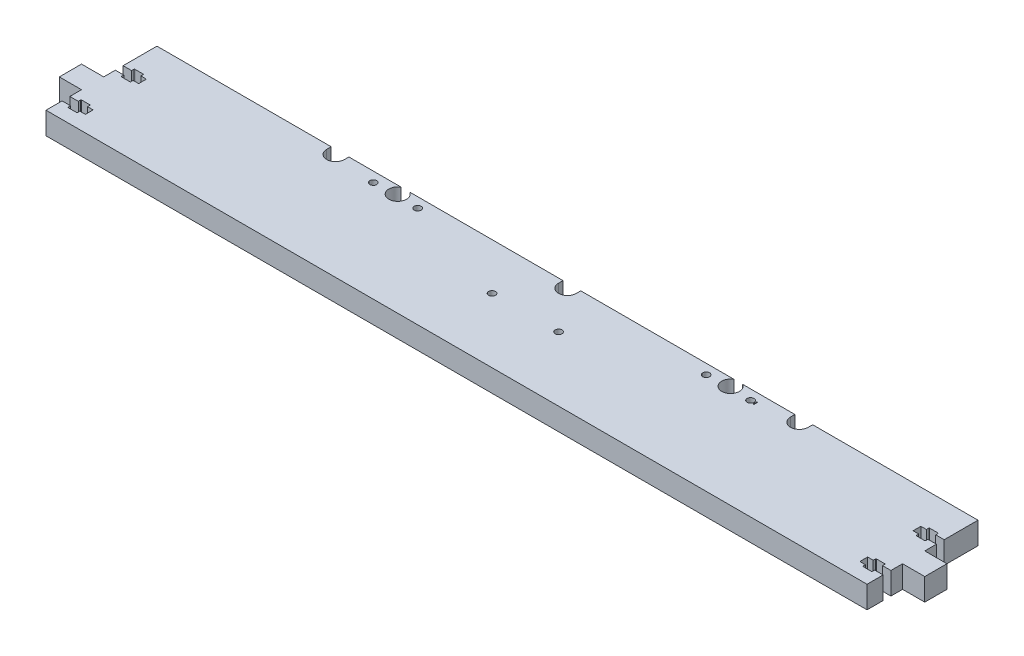
SolidWorks part; units mm, degrees
ref_plane "Front Plane" through (0, 0, 0) normal (0, 0, 1) x (1, 0, 0)
ref_plane "Top Plane" through (0, 0, 0) normal (0, 1, 0) x (1, 0, 0)
ref_plane "Right Plane" through (0, 0, 0) normal (1, 0, 0) x (0, 0, -1)
sketch "Sketch1" plane through (0, 0, 0) normal (0, 1, 0) x (1, 0, 0)
  line L0 (0, 25) -> (0, -25)
  line L1 (-185, 25) -> (0, 25)
  line L2 (-185, 25) -> (-185, -25) construction
  line L3 (-185, -25) -> (0, -25)
  line L4 (-185, -4) -> (-195, -4) construction
  line L5 (-185, 25) -> (0, 0) construction
  line L6 (-185, -25) -> (0, 0) construction
  line L7 (-185, -9) -> (-195, -9)
  line L8 (-195, -9) -> (-195, 1)
  line L9 (-195, 1) -> (-185, 1)
  line L10 (-185, 1) -> (-185, 25)
  line L11 (-185, -9) -> (-185, -25)
  line L47 (0, -25) -> (0, 25) construction
  line L89 (0, -25) -> (0, 25) construction
  point P0 (0, 0)
  dimension "D1" = 185
  dimension "D25" = 25
  dimension "D4" = 50
  dimension "D3" = 21
  dimension "D5" = 10
  dimension "D6" = 10
  dimension "D7" = 5
extrude "MainBody" add sketch "Sketch1" along normal blind 10 contours L3 region at (-93.5428, 0, 0.0428)
sketch "Sketch5" plane through (0, 10, 0) normal (0, 1, 0) x (1, 0, 0)
  line L0 (-185, 8) -> (-174.5, 8) construction
  line L1 (-185, 1) -> (-185, 25) construction
  line L2 (-185, 9.75) -> (-174.5, 9.75) construction
  line L3 (-174.5, 9.75) -> (-174.5, 6.25) construction
  line L4 (-174.5, 6.25) -> (-185, 6.25) construction
  line L5 (-185, 9.75) -> (-181.2, 9.75)
  line L6 (-181.2, 9.75) -> (-181.2, 10.75)
  line L7 (-180.95, 11) -> (-177.25, 11)
  line L8 (-177, 10.75) -> (-177, 9.75)
  line L9 (-177, 9.75) -> (-174.5, 9.75)
  line L10 (-174.5, 9.75) -> (-174.5, 6.25)
  line L11 (-185, 6.25) -> (-185, 9.75)
  line L12 (-195, -9) -> (-195, 1) construction
  line L13 (-185, 6.25) -> (-174.5, 6.25) construction
  line L14 (-177, 6.25) -> (-174.5, 6.25)
  line L15 (-177, 5.25) -> (-177, 6.25)
  line L16 (-180.95, 5) -> (-177.25, 5)
  line L17 (-181.2, 6.25) -> (-181.2, 5.25)
  line L18 (-185, 6.25) -> (-181.2, 6.25)
  line L19 (-185, 1) -> (-185, -9) construction
  line L20 (-195, -4) -> (-185, -4) construction
  line L21 (-195, -9) -> (-195, 1) construction
  line L22 (-185, -14.25) -> (-174.5, -14.25) construction
  line L23 (-174.5, -14.25) -> (-185, -14.25) construction
  line L24 (-174.5, -17.75) -> (-174.5, -14.25) construction
  line L25 (-185, -17.75) -> (-174.5, -17.75) construction
  line L26 (-185, -16) -> (-174.5, -16) construction
  line L27 (-185, -14.25) -> (-181.2, -14.25)
  line L28 (-181.2, -14.25) -> (-181.2, -13.25)
  line L29 (-180.95, -13) -> (-177.25, -13)
  line L30 (-177, -13.25) -> (-177, -14.25)
  line L31 (-177, -14.25) -> (-174.5, -14.25)
  line L32 (-185, -14.25) -> (-185, -17.75)
  line L33 (-174.5, -17.75) -> (-174.5, -14.25)
  line L34 (-177, -17.75) -> (-174.5, -17.75)
  line L35 (-177, -18.75) -> (-177, -17.75)
  line L36 (-180.95, -19) -> (-177.25, -19)
  line L37 (-181.2, -17.75) -> (-181.2, -18.75)
  line L38 (-185, -17.75) -> (-181.2, -17.75)
  line L39 (-185, 6.25) -> (-174.5, 6.25) construction
  arc A0 (-177.25, 11) -> (-177, 10.75) centre (-177.25, 10.75) cw
  arc A1 (-181.2, 10.75) -> (-180.95, 11) centre (-180.95, 10.75) cw
  arc A2 (-181.2, 5.25) -> (-180.95, 5) centre (-180.95, 5.25) ccw
  arc A3 (-177.25, 5) -> (-177, 5.25) centre (-177.25, 5.25) ccw
  arc A4 (-177.25, -13) -> (-177, -13.25) centre (-177.25, -13.25) cw
  arc A5 (-181.2, -13.25) -> (-180.95, -13) centre (-180.95, -13.25) cw
  arc A6 (-181.2, -18.75) -> (-180.95, -19) centre (-180.95, -18.75) ccw
  arc A7 (-177.25, -19) -> (-177, -18.75) centre (-177.25, -18.75) ccw
  point P6 (-195, -4)
  point P17 (-177, 11)
  point P20 (-181.2, 11)
  point P29 (-181.2, 5)
  point P30 (-177, 5)
  point P61 (-177, -13)
  point P62 (-181.2, -13)
  point P63 (-181.2, -19)
  point P64 (-177, -19)
  dimension "D8" = 0.25
  dimension "D1" = 10.5
  dimension "D2" = 1.75
  dimension "D4" = 4.2
  dimension "D5" = 8
  dimension "D6" = 3
  dimension "D7" = 12
extrude "ScrewCutouts" cut sketch "Sketch5" against normal through all
mirror "Mirror1" about plane through (0, 0, 0) normal (1, 0, 0) of "ScrewCutouts", "MainBody"
sketch "Sketch3" plane through (0, 10, 0) normal (0, 1, 0) x (1, 0, 0)
  line L0 (2, 25) -> (2, -25) construction
  line L1 (-185, 25) -> (185, 25) construction
  line L2 (-185, -25) -> (185, -25) construction
  line L3 (-63, 20.5) -> (-83, 20.5) construction
  line L4 (-73, 17.5) -> (-73, 25.5) construction
  line L5 (77, 17.5) -> (77, 25.5) construction
  line L6 (67, 20.5) -> (87, 20.5) construction
  circle A0 centre (-73, 21.5) radius 4
  circle A1 centre (-83, 20.5) radius 1.55
  circle A2 centre (-63, 20.5) radius 1.55
  circle A3 centre (67, 20.5) radius 1.55
  circle A4 centre (87, 20.5) radius 1.55
  circle A5 centre (77, 21.5) radius 4
  dimension "D2" = 8
  dimension "D4" = 3.1
  dimension "D1" = 3.5
  dimension "D5" = 75
  dimension "D6" = 2
  dimension "D3" = 10
  dimension "D7" = 1
extrude "RodCutouts" cut sketch "Sketch3" against normal through all
sketch "Sketch6" plane through (0, 10, 0) normal (0, 1, 0) x (1, 0, 0)
  line L0 (-73, 21.5) -> (77, 21.5) construction
  line L1 (2, 21.5) -> (2, -25) construction
  line L2 (-185, -25) -> (185, -25) construction
  line L3 (17, 4) -> (-13, 4) construction
  line L4 (-71.0635, 25) -> (75.0635, 25) construction
  circle A0 centre (-13, 4) radius 1.55
  circle A1 centre (17, 4) radius 1.55
  point P13 (2, 4)
  dimension "D3" = 21
  dimension "D1" = 3.1
  dimension "D2" = 15
extrude "Cut-Extrude1" cut sketch "Sketch6" against normal through all
sketch "Sketch7" plane through (0, 10, 0) normal (0, 1, 0) x (1, 0, 0)
  line L0 (-73, 21.5) -> (77, 21.5) construction
  line L1 (2, 21.5) -> (2, -25) construction
  line L3 (-102.5, 25) -> (-102.5, 23) construction
  line L4 (-185, 25) -> (-74.9365, 25) construction
  line L5 (-98.5, 25) -> (-98.5, 23)
  line L6 (-106.5, 25) -> (-106.5, 23)
  line L7 (106.5, 25) -> (106.5, 23) construction
  line L8 (102.5, 25) -> (102.5, 23)
  line L9 (110.5, 25) -> (110.5, 23)
  line L12 (-185, -25) -> (185, -25) construction
  arc A0 (-98.5, 25) -> (-106.5, 25) centre (-102.5, 25) ccw
  arc A1 (-106.5, 23) -> (-98.5, 23) centre (-102.5, 23) ccw
  arc A2 (102.5, 25) -> (110.5, 25) centre (106.5, 25) cw
  arc A3 (110.5, 23) -> (102.5, 23) centre (106.5, 23) cw
  point P12 (-102.5, 24)
  point P19 (106.5, 24)
  dimension "D1" = 4
  dimension "D2" = 2
  dimension "D3" = 104.5
extrude "BedAdjustmentScrewCutout" cut sketch "Sketch7" against normal through all
sketch "Sketch8" plane through (0, 10, 0) normal (0, 1, 0) x (1, 0, 0)
  line L0 (88.35, 20.5) -> (89.35, 20.5) construction
  line L1 (88.55, 20.5) -> (88.55, 25) construction
  line L2 (88.35, 20.5) -> (89.35, 21.5)
  line L3 (89.35, 21.5) -> (89.35, 19.5)
  line L4 (88.35, 20.5) -> (89.35, 19.5)
  line L5 (78.9365, 25) -> (102.5, 25) construction
  circle A1 centre (87, 20.5) radius 1.55 construction
  point P9 (89.35, 20.5)
  dimension "D1" = 1
  dimension "D2" = 1
  dimension "D3" = 0.2
extrude "DirectionKey" cut sketch "Sketch8" against normal through all
sketch "Sketch9" plane through (0, 10, 0) normal (0, 1, 0) x (1, 0, 0)
  line L0 (-13, 4) -> (17, 4) construction
  line L1 (2, 4) -> (2, 25) construction
  line L2 (-71.0635, 25) -> (75.0635, 25) construction
  line L3 (2, 27) -> (2, 23) construction
  line L4 (6, 27) -> (6, 23)
  line L5 (-2, 27) -> (-2, 23)
  arc A0 (6, 27) -> (-2, 27) centre (2, 27) ccw
  arc A1 (-2, 23) -> (6, 23) centre (2, 23) ccw
  point P10 (2, 25)
  dimension "D1" = 4
  dimension "D2" = 2
extrude "Cut-Extrude2" cut sketch "Sketch9" against normal through all
equation "\"Y-ROD-SPACING\"=75"
equation "\"Y-BED-OFFSET\"=2"
equation "\"T-SLOT-NUT-FILLET-RADIUS\"=0.25"
equation "\"T-SLOT-SCREW-SHAFT-RADIUS\"=1.75"
equation "\"T-SLOT-SCREW-SHAFT-CUTOUT-LENGTH\"=10.5"
equation "\"T-SLOT-NUT-DEPTH\"=4.2"
equation "\"T-SLOT-NUT-WIDTH\"=3"
equation "\"T-SLOT-NUT-END-DISTANCE\"=8"
equation "\"ACRYLIC-TAB-CUTOUT-SIZE\"=\"ACRYLIC-THICKNESS\"+\"ACRYLIC-TAB-TOLERANCE\"*2"
equation "\"ACRYLIC-M3-HOLE\"=3.1"
equation "\"D1@Sketch5\"=\"T-SLOT-SCREW-SHAFT-CUTOUT-LENGTH\""
equation "\"D2@Sketch5\"=\"T-SLOT-SCREW-SHAFT-RADIUS\""
equation "\"D4@Sketch5\"=\"T-SLOT-NUT-DEPTH\""
equation "\"D5@Sketch5\"=\"T-SLOT-NUT-END-DISTANCE\""
equation "\"D6@Sketch5\"=\"T-SLOT-NUT-WIDTH\""
equation "\"D8@Sketch5\"=\"T-SLOT-NUT-FILLET-RADIUS\""
equation "\"D4@Sketch3\"=\"ACRYLIC-M3-HOLE\""
equation "\"D5@Sketch3\"=\"Y-ROD-SPACING\""
equation "\"D6@Sketch3\"=\"Y-BED-OFFSET\""
equation "\"Y-BED-ROD-INSET\"=3.5"
equation "\"D1@Sketch3\"=\"Y-BED-ROD-INSET\""
equation "\"SMOOTHROD-CAP-SCREW-DISTANCE\"=20"
equation "\"D3@Sketch3\"=\"SMOOTHROD-CAP-SCREW-DISTANCE\"/2"
equation "\"ACRYLIC-TAB-WIDTH\"=\"ACRYLIC-THICKNESS\""
equation "\"FRAME-WIDTH-INNER\"=370"
equation "\"D6@Sketch1\"=\"ACRYLIC-TAB-WIDTH\""
equation "\"D5@Sketch1\"=\"ACRYLIC-TAB-WIDTH\""
equation "\"D1@Sketch1\"=\"FRAME-WIDTH-INNER\"/2"
equation "\"X-ROD-SPACING\"=45"
equation "\"Z-ROD-SPACING\"=17.5"
equation "\"ACRYLIC-THICKNESS\"=10"
equation "\"ACRYLIC-THICKNESS2\"=4.5"
equation "\"NEMA17-HOLE-SPACING\"=31"
equation "\"NEMA17-CENTRAL-CUTOUT\"=22.5"
equation "\"Z-BRACKET-REACH\"=55"
equation "\"TOP-BRACKET-SPACING\"=40"
equation "\"SMOOTHROD-X-LENGTH\"=350"
equation "\"SMOOTHROD-Y-LENGTH\"=350"
equation "\"SMOOTHROD-Z-LENGTH\"=350"
equation "\"SMOOTHROD-TIGHTENING-HEADROOM\"=.25"
equation "\"LEADSCREW-Z-LENGTH\"=300"
equation "\"SCREW-LENGTH-FRAME\"=\"ACRYLIC-THICKNESS\" + 10"
equation "\"SCREW-HEAD-RADIUS\"=6"
equation "\"PRINTED-X-SMOOTHROD-DIAMETER\"=8.2"
equation "\"PRINTED-X-SMOOTHROD-CUTOUT\"=10"
equation "\"PRINTED-X-BASE-HEIGHT\"=10"
equation "\"PRINTED-LM8UU-CUTOUT-SIZE\"=15.25"
equation "\"PRINTED-LM8UU-CUTOUT-LENGTH\"=24.5"
equation "\"PRINTED-X-IDLER-HEIGHT\"=16"
equation "\"PSU-MOUNTING-WIDTH\"=95"
equation "\"PSU-MOUNTING-HEIGHT\"=177"
equation "\"D1@MainBody\"=\"ACRYLIC-THICKNESS\""
equation "\"D7@Sketch1\"=\"ACRYLIC-TAB-WIDTH\"/2"
equation "\"D1@Sketch6\"=\"ACRYLIC-M3-HOLE\""
equation "\"Y-BELT-TO-ROD-DISTANCE\"=20"
equation "\"Y-BED-SCREW-SPACING\"=209"
equation "\"Z-ROD-INSET\"=16"
equation "\"SPOOL-HOLDER-ROD-SPACING\"=150"
equation "\"D3@Sketch7\"=\"Y-BED-SCREW-SPACING\"/2"
equation "\"Y-BED-SCREW-CUTOUT-SLOT-HEIGHT\"=2"
equation "\"D2@Sketch7\"=\"Y-BED-SCREW-CUTOUT-SLOT-HEIGHT\""
equation "\"ACRYLIC-TAB-TOLERANCE\"=.1"
equation "\"SCREW-LENGTH-MOTOR\"=\"ACRYLIC-THICKNESS\" + 5"
equation "\"SCREW-LENGTH-EXTRUDER\"=28"
equation "\"PRINTED-M3-HOLE\"=3.5"
equation "\"ACRYLIC-X-CARRIAGE-WIDTH\"=55"
equation "\"ACRYLIC-X-CARRIAGE-HEIGHT\"=75"
equation "\"ACRYLIC-X-CARRIAGE-LM8UU-CUTOUT-WIDTH\"=24.25"
equation "\"ACRYLIC-X-CARRIAGE-LM8UU-CUTOUT-HEIGHT\"=11.5"
equation "\"ACRYLIC-X-CARRIAGE-SCREW-SPACING-X\"=15"
equation "\"ACRYLIC-X-CARRIAGE-SCREW-SPACING-Y\"=33"
equation "\"ACRYLIC-X-CARRIAGE-CENTER-TAB-SPACING\"=14"
equation "\"ACRYLIC-X-CARRIAGE-EXTRUDER-OFFSET\"=26"
equation "\"ACRYLIC-X-CARRIAGE-EXTRUDER-ANGLE\"=90"
equation "\"ACRYLIC-X-CARRIAGE-EXTRUDER-SHELF-DEPTH\"=\"ACRYLIC-X-CARRIAGE-EXTRUDER-OFFSET\" + 28"
equation "\"ACRYLIC-X-CARRIAGE-EXTRUDER-BRACE-SPACING\"=23"
equation "\"ACRYLIC-X-CARRIAGE-EXTRUDER-BRACE-TAB-OFFSET\"=20"
equation "\"ACRYLIC-X-CARRIAGE-EXTRUDER-BRACE-HEIGHT\"=35"
equation "\"ACRYLIC-X-CARRIAGE-EXTRUDER-BRACE-SCREW-SPACING\"=22"
equation "\"ACRYLIC-X-CARRIAGE-DUAL-WIDTH-MULTIPLIER\"=1.65"
equation "\"ACRYLIC-X-CARRIAGE-DUAL-HOTEND-SPACING\"=42"
equation "\"ACRYLIC-X-CARRIAGE-DUAL-WIDTH\"=95"
equation "\"ACRYLIC-X-CARRIAGE-DUAL-HOTEND-SEPARATION\"=35"
equation "\"ACRYLIC-X-CARRIAGE-DUAL-MOUNT-PLATE-DEPTH\"=75"
equation "\"ACRYLIC-X-CARRIAGE-DUAL-MOUNT-BRACE-WIDTH\"=33"
equation "\"ACRYLIC-X-CARRIAGE-DUAL-MOUNT-SCREW-WIDTH\"=40"
equation "\"BLOWER-FAN-WIDTH\"=15"
equation "\"D2@Sketch9\"=\"Y-BED-SCREW-CUTOUT-SLOT-HEIGHT\""
